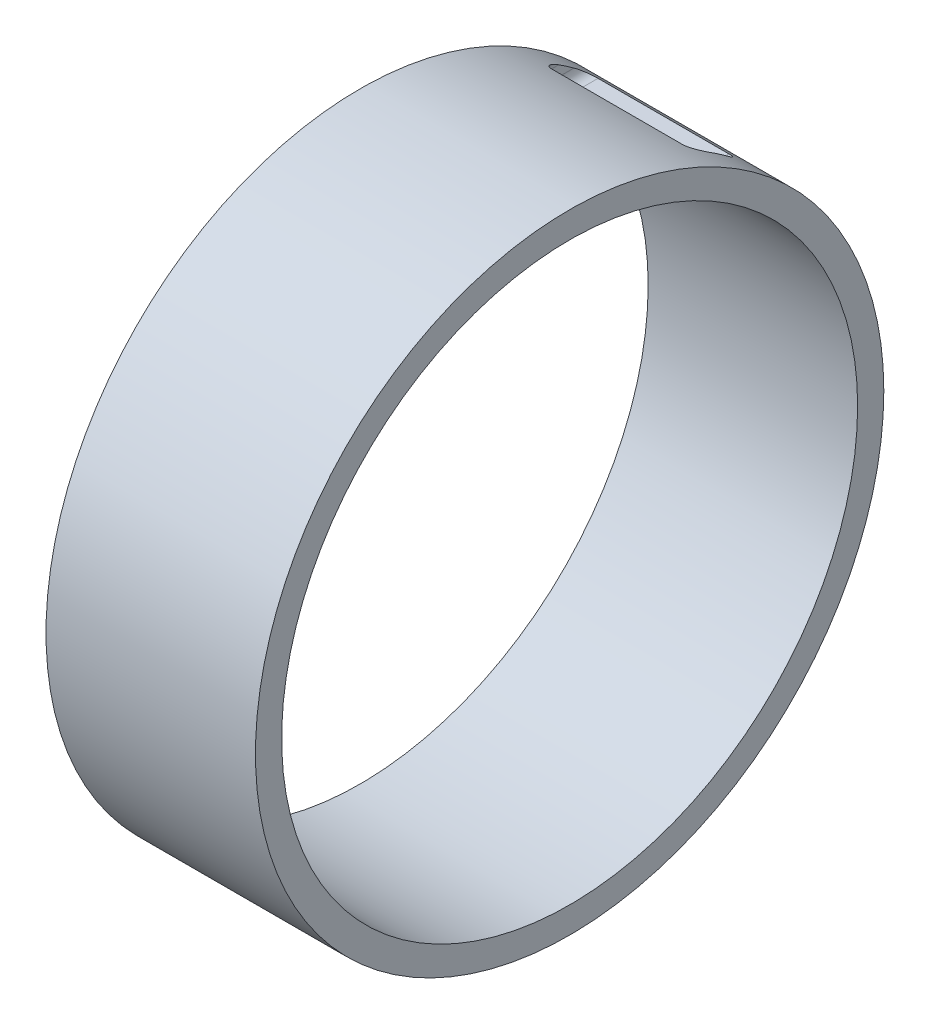
SolidWorks part; units mm, degrees
material "6061-T6 (SS)"
ref_plane "Front Plane" through (0, 0, 0) normal (0, 0, 1) x (1, 0, 0)
ref_plane "Top Plane" through (0, 0, 0) normal (0, 1, 0) x (1, 0, 0)
ref_plane "Right Plane" through (0, 0, 0) normal (1, 0, 0) x (0, 0, -1)
sketch "Sketch1" plane through (0, 0, 0) normal (1, 0, 0) x (0, 0, -1)
  circle A0 centre (0, 0) radius 69.85
  circle A1 centre (0, 0) radius 76.2
  dimension "D1" = 6.35
  dimension "D2" = 139.7
extrude "Boss-Extrude1" add sketch "Sketch1" along normal mid plane 50.8
ref_plane "Plane1" through (6.35, 0, 0) normal (1, 0, 0) x (0, 0, -1)
ref_plane "Plane2" through (-6.35, 0, 0) normal (-1, 0, 0) x (0, 0, 1)
ref_axis "Axis1" through (25.4, 0, 0) along (-1, 0, 0)
sketch "Sketch4" plane through (0, 0, 0) normal (0, 0, 1) x (1, 0, 0)
  line L0 (0, -76.2) -> (0, 76.2) construction
  line L1 (-18.415, 66.675) -> (18.415, 66.675)
  line L2 (-18.415, 66.675) -> (-18.415, 59.055)
  line L3 (-18.415, 59.055) -> (18.415, 59.055)
  line L4 (18.415, 66.675) -> (18.415, 59.055)
  line L9 (25.4, 76.2) -> (-25.4, 76.2) construction
  point P4 (0, 59.055)
  dimension "D1" = 36.83
  dimension "D3" = 7.62
  dimension "D4" = 9.525
extrude "Cut-Extrude1" cut sketch "Sketch4" against normal up to surface (36.8902 mm away) up to face at (25.4, 0, -76.2)
fillet "Fillet1" radius 2.54 4 edges at (-18.415, 59.055, -42.7293) (-18.415, 66.675, -28.855) (18.415, 66.675, -28.855) (18.415, 59.055, -42.7293)
